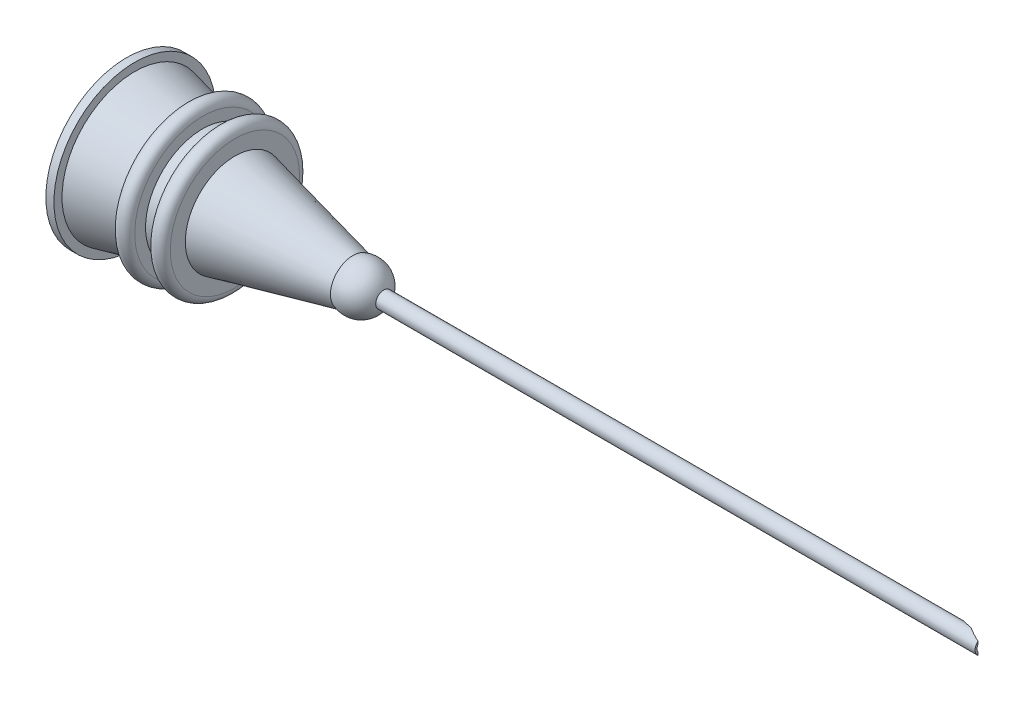
SolidWorks part; units mm, degrees
ref_plane "Front Plane" through (0, 0, 0) normal (0, 0, 1) x (1, 0, 0)
ref_plane "Top Plane" through (0, 0, 0) normal (0, 1, 0) x (1, 0, 0)
ref_plane "Right Plane" through (0, 0, 0) normal (1, 0, 0) x (0, 0, -1)
sketch "Sketch2" plane through (0, 0, 0) normal (0, 0, 1) x (1, 0, 0)
  line L0 (0, 0) -> (0, 1.3888)
  line L1 (0, 1.3888) -> (-7.3, 3.0708)
  line L2 (-13.5, 4.4994) -> (-13.5, 5)
  line L3 (-13.5, 5) -> (-14, 5)
  line L4 (-14, 5) -> (-14, 3.845)
  line L5 (-14, 3.845) -> (-1, 0.8496)
  line L6 (-1, 0.8496) -> (-1, 0)
  line L7 (-1, 0) -> (0, 0)
  line L8 (-1, 0) -> (-14.886, 0) construction
  line L9 (-7.3, 4) -> (-7.3, 3.0708)
  line L10 (-8.3, 4) -> (-8.3, 3.3013)
  line L11 (-9.3, 4.2) -> (-9.3, 3.5317)
  line L12 (-8.3, 3.3013) -> (-9.3, 3.5317)
  line L13 (-10.3, 4.2) -> (-10.3, 3.7621)
  line L14 (-10.3, 3.7621) -> (-13.5, 4.4994)
  arc A0 (-9.3, 4.2) -> (-10.3, 4.2) centre (-9.8, 4.2) ccw
  arc A1 (-7.3, 4) -> (-8.3, 4) centre (-7.8, 4) ccw
  dimension "D6" = 1
  dimension "D7" = 1
  dimension "D1" = 0.5
  dimension "D2" = 1
  dimension "D3" = 0.75
  dimension "D4" = 2
  dimension "D5" = 14
  dimension "D8" = 4.2
  dimension "D9" = 4
  dimension "D10" = 7.8
revolve "Revolve1" add sketch "Sketch2" angle 360 about L8
dome "Dome1" faces to dome 1 distance 2 reverse direction no elliptical dome no face at (0, 0, -1.3888) parameters "D1"=2
sketch "Sketch4" plane through (-1, 0, 0) normal (-1, 0, 0) x (0, 0, 1)
  circle A0 centre (0, 0) radius 0.5
  dimension "D1" = 1
extrude "Cut-Extrude1" cut sketch "Sketch4" against normal through all
sketch "Sketch5" plane through (-1, 0, 0) normal (-1, 0, 0) x (0, 0, 1)
  circle A0 centre (0, 0) radius 0.5 construction
  circle A1 centre (0, 0) radius 0.5
extrude "Extrude-Thin1" add sketch "Sketch5" against normal blind 40 thin thin type one direction reverse wall 0.125
sketch "Sketch6" plane through (0, 0, 0) normal (0, 1, 0) x (1, 0, 0)
  line L0 (39, 0) -> (39, 3.4719) construction
  line L1 (39, -0.5) -> (39, 0.5) construction
  circle A0 centre (39, 3.4719) radius 3.5
  point P5 (39, 3.4719)
  dimension "D1" = 7
extrude "Cut-Extrude2" cut sketch "Sketch6" against normal through all and the other way through all
sketch "Sketch7" plane through (0, 0, 0) normal (0, 1, 0) x (1, 0, 0)
  line L0 (39, -0.2641) -> (39, 4.5446) construction
  line L1 (39, -0.5) -> (39, -0.0281) construction
  line L2 (39, -0.2641) -> (41, -0.2641) construction
  line L3 (41, -0.2641) -> (41, 2.827) construction
  circle A4 centre (39.7983, 2.3742) radius 2.8072
  dimension "D1" = 2
extrude "Cut-Extrude3" cut sketch "Sketch7" against normal through all and the other way through all
